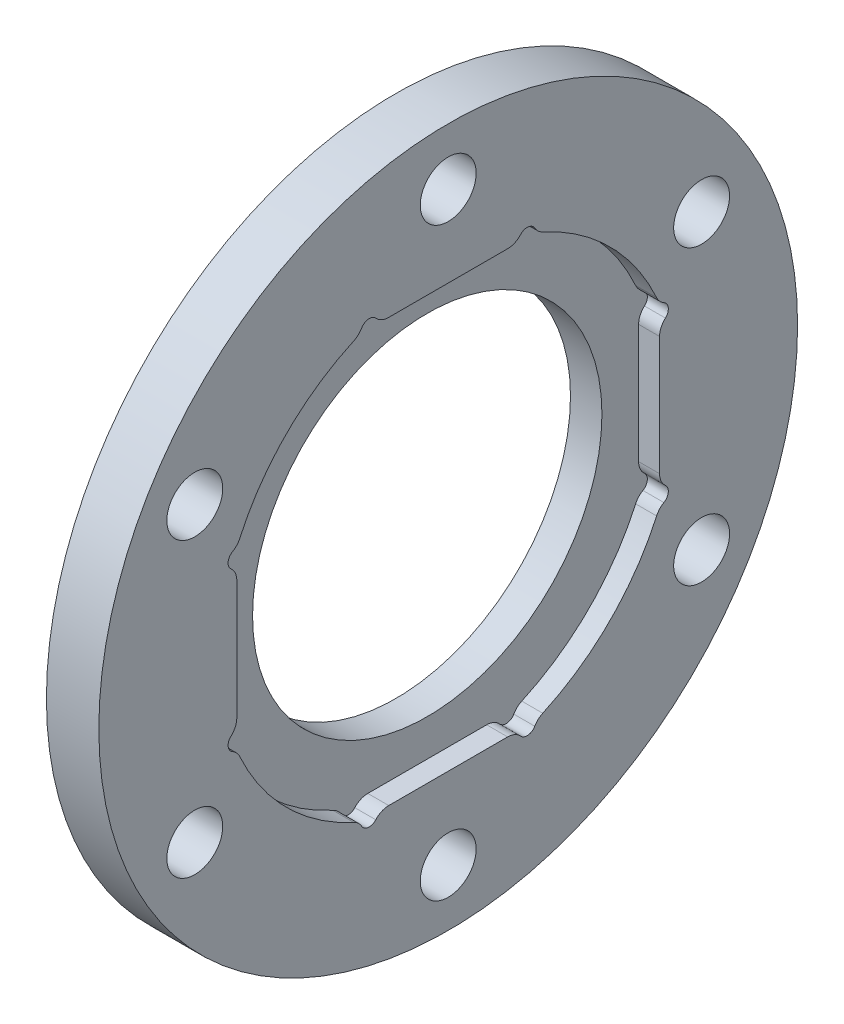
SolidWorks part; units mm, degrees
ref_plane "Front Plane" through (0, 0, 0) normal (0, 0, 1) x (1, 0, 0)
ref_plane "Top Plane" through (0, 0, 0) normal (0, 1, 0) x (1, 0, 0)
ref_plane "Right Plane" through (0, 0, 0) normal (1, 0, 0) x (0, 0, -1)
other "Configuration Table"
sketch "草图3" plane through (0, 0, 0) normal (1, 0, 0) x (0, 0, -1)
  circle A0 centre (0, 0) radius 20
  dimension "D1" = 40
extrude "凸台-拉伸3" add sketch "草图3" along normal blind 3
sketch "草图4" plane through (3, 0, 0) normal (1, 0, 0) x (0, 0, -1)
  circle A0 centre (0, 0) radius 13.1
extrude "切除-拉伸1" cut sketch "草图4" against normal blind 1.2
sketch "草图5" plane through (1.8, 0, 0) normal (1, 0, 0) x (0, 0, -1)
  line L5 (-5.02, 12.1) -> (5.02, 12.1)
  line L6 (-12.1, 5.02) -> (-12.1, -5.02)
  line L7 (-5.02, -12.1) -> (5.02, -12.1)
  line L8 (12.1, 5.02) -> (12.1, -5.02)
  arc A4 (-12.1, 5.02) -> (-12.1, -5.02) centre (0, 0) ccw
  arc A5 (5.02, 12.1) -> (-5.02, 12.1) centre (0, 0) ccw
  arc A6 (12.1, -5.02) -> (12.1, 5.02) centre (0, 0) ccw
  arc A7 (-5.02, -12.1) -> (5.02, -12.1) centre (0, 0) ccw
extrude "凸台-拉伸4" add sketch "草图5" along normal blind 1.2
sketch "草图6" plane through (1.8, 0, 0) normal (1, 0, 0) x (0, 0, -1)
  circle A0 centre (0, 0) radius 10
extrude "切除-拉伸2" cut sketch "草图6" against normal through all
sketch "草图7" plane through (3, 0, 0) normal (1, 0, 0) x (0, 0, -1)
  line L0 (0, 0) -> (0, 16.75) construction
  circle A0 centre (0, 16.75) radius 1.6
  circle A1 centre (14.5059, 8.375) radius 1.6
  circle A2 centre (14.5059, -8.375) radius 1.6
  circle A3 centre (0, -16.75) radius 1.6
  circle A4 centre (-14.5059, -8.375) radius 1.6
  circle A5 centre (-14.5059, 8.375) radius 1.6
  point P17 (0, 0)
  dimension "D1" = 6
extrude "切除-拉伸4" cut sketch "草图7" against normal through all
sketch "草图8" plane through (3, 0, 0) normal (1, 0, 0) x (0, 0, -1)
  line L0 (-5.02, 12.1) -> (-4.52, 12.1) construction
  line L1 (-5.02, 12.1) -> (5.02, 12.1) construction
  line L2 (12.1, 5.02) -> (12.1, 4.52) construction
  line L3 (5.02, -12.1) -> (4.52, -12.1) construction
  line L4 (-12.1, -5.02) -> (-12.1, -4.52) construction
  line L5 (5.02, 12.1) -> (4.52, 12.1) construction
  line L6 (12.1, -5.02) -> (12.1, -4.52) construction
  line L7 (-5.02, -12.1) -> (-4.52, -12.1) construction
  line L8 (-12.1, 5.02) -> (-12.1, 4.52) construction
  circle A0 centre (-4.52, 12.1) radius 0.5
  circle A1 centre (12.1, 4.52) radius 0.5
  circle A2 centre (4.52, -12.1) radius 0.5
  circle A3 centre (-12.1, -4.52) radius 0.5
  circle A4 centre (4.52, 12.1) radius 0.5
  circle A5 centre (12.1, -4.52) radius 0.5
  circle A6 centre (-4.52, -12.1) radius 0.5
  circle A7 centre (-12.1, 4.52) radius 0.5
  point P18 (0, 0)
  point P32 (0, 0)
  dimension "D1" = 4
  dimension "D2" = 4
extrude "切除-拉伸5" cut sketch "草图8" against normal up to surface (1.2 mm away) up to face at (1.8, 0, -10)
fillet "圆角1" radius 1 16 edges at (2.4, 4.02, -12.1) (2.4, 5.02, -12.1) (2.4, -5.02, -12.1) (2.4, -4.02, -12.1) (2.4, -12.1, -5.02) (2.4, -12.1, -4.02) (2.4, -12.1, 4.02) (2.4, -12.1, 5.02) (2.4, -5.02, 12.1) (2.4, -4.02, 12.1) (2.4, 4.02, 12.1) (2.4, 5.02, 12.1) (2.4, 12.1, 5.02) (2.4, 12.1, 4.02) (2.4, 12.1, -4.02) (2.4, 12.1, -5.02)
